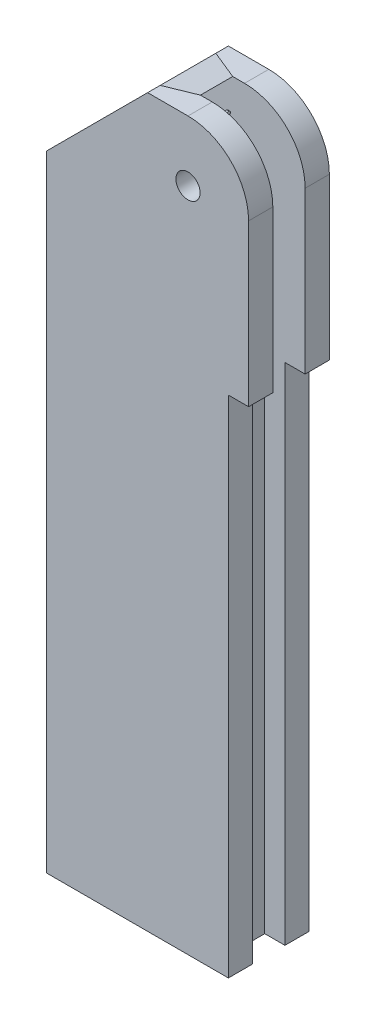
SolidWorks part; units mm, degrees
ref_plane "Plan de face" through (0, 0, 0) normal (0, 0, 1) x (1, 0, 0)
ref_plane "Plan de dessus" through (0, 0, 0) normal (0, 1, 0) x (1, 0, 0)
ref_plane "Plan de droite" through (0, 0, 0) normal (1, 0, 0) x (0, 0, -1)
sketch "Esquisse1" plane through (0, 0, 0) normal (0, 0, 1) x (1, 0, 0)
  line L0 (-35, -10) -> (-10, 15)
  line L1 (-10, 15) -> (0, 15)
  line L2 (15, 0) -> (15, -39.85)
  line L3 (15, -39.85) -> (10, -39.85)
  line L4 (10, -39.85) -> (10, -164.85)
  line L5 (10, -164.85) -> (-35, -164.85)
  line L6 (-35, -164.85) -> (-35, -10)
  line L7 (-41.5629, 0) -> (66.529, 0) construction
  line L8 (-49.1609, -51.85) -> (34.1445, -51.85) construction
  circle A0 centre (0, 0) radius 3
  arc A1 (0, 15) -> (15, 0) centre (0, 0) cw
  dimension "D1" = 6
  dimension "D7" = 15
  dimension "D2" = 50
  dimension "D3" = 10
  dimension "D4" = 45
  dimension "D5" = 5
  dimension "D6" = 15
  dimension "D8" = 125
  dimension "D10" = 51.85
  dimension "D11" = 12
  dimension "D12" = 15
extrude "Extrusion1" add sketch "Esquisse1" along normal blind 10 and the other way blind 10
sketch "Esquisse2" plane through (15, 0, 0) normal (1, 0, 0) x (0, 0, -1)
  line L0 (-10, 15) -> (10, 15) construction
  line L1 (-4, -15) -> (4, -15)
  line L2 (-4, -15) -> (-4, 23.995)
  line L3 (-4, 23.995) -> (4, 23.995)
  line L4 (4, -15) -> (4, 23.995)
  dimension "D1" = 8
  dimension "D2" = 4
  dimension "D3" = 30
extrude "Enlèv. mat.-Extru.2" cut sketch "Esquisse2" against normal through all
chamfer "Chanfrein1" distance 5 angle 30 2 edges at (-22.5, 2.5, 4) (-22.5, 2.5, -4) first distance on face at (3, 0, 4) first distance on face at (-3, 0, -4)
sketch "Esquisse3" plane through (0, -15, 0) normal (0, 1, 0) x (-1, 0, 0)
  line L1 (-5, 4) -> (-15.5853, 4)
  line L2 (-5, 4) -> (-5, -4)
  line L3 (-5, -4) -> (-15.5853, -4)
  line L4 (-15.5853, 4) -> (-15.5853, -4)
  line L6 (-15, 10) -> (-15, 4) construction
  dimension "D1" = 10
extrude "Enlèv. mat.-Extru.3" cut sketch "Esquisse3" against normal through all
ref_plane "Plan1" through (0, 10.5, 0) normal (0, 1, 0) x (-1, 0, 0)
ref_point "Point1"
sketch "Esquisse4" plane through (0, 0, 0) normal (1, 0, 0) x (0, 0, -1)
  circle A0 centre (0, 10.5) radius 0.5
  dimension "D1" = 1
extrude "Extrusion2" add sketch "Esquisse4" against normal blind 0.5
